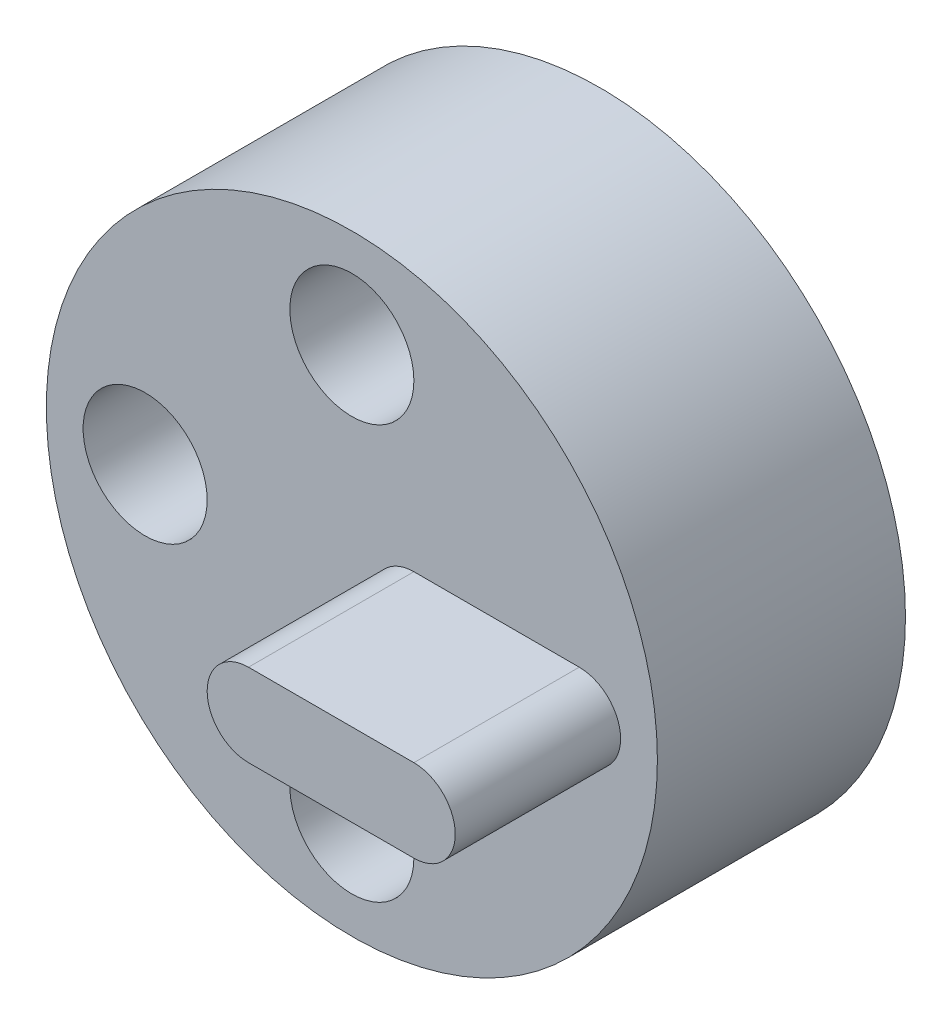
SolidWorks part; units mm, degrees
ref_plane "Front Plane" through (0, 0, 0) normal (0, 0, 1) x (1, 0, 0)
ref_plane "Top Plane" through (0, 0, 0) normal (0, 1, 0) x (1, 0, 0)
ref_plane "Right Plane" through (0, 0, 0) normal (1, 0, 0) x (0, 0, -1)
sketch "Sketch1" plane through (0, 0, 0) normal (0, 0, 1) x (1, 0, 0)
  line L0 (5.5, 0) -> (1.5, 0) construction
  line L1 (5.5, -1) -> (1.5, -1)
  line L2 (5.5, 1) -> (1.5, 1)
  line L3 (0, 0) -> (0, 5) construction
  circle A0 centre (0, 0) radius 7.39
  arc A1 (5.5, -1) -> (5.5, 1) centre (5.5, 0) ccw
  arc A2 (1.5, 1) -> (1.5, -1) centre (1.5, 0) ccw
  circle A3 centre (0, 5) radius 1.5
  circle A4 centre (-5, 0) radius 1.5
  circle A5 centre (0, -5) radius 1.5
  point P5 (3.5, 0)
  dimension "D1" = 14.78
  dimension "D4" = 1
  dimension "D5" = 3
  dimension "D2" = 4
  dimension "D3" = 1.5
  dimension "D6" = 5
  dimension "D7" = 3
extrude "Boss-Extrude1" add sketch "Sketch1" along normal blind 6 contours A0 A5 A4 A3 A2 L2 A1 L1 region at (-0.0262, 0, 0)
extrude "Boss-Extrude2" add sketch "Sketch1<3>" along normal blind 10 contours L2 A2 L1 A1 region at (3.5, 0, 0)
sketch "Sketch1<3>" plane through (0, 0, 0) normal (0, 0, 1) x (1, 0, 0) same geometry as "Sketch1"
sketch "Sketch2" plane through (0, 0, 0) normal (0, 0, -1) x (-1, 0, 0)
  circle A0 centre (0, 0) radius 2.65
  dimension "D1" = 5.3
extrude "Cut-Extrude1" cut sketch "Sketch2" against normal blind 4.3
